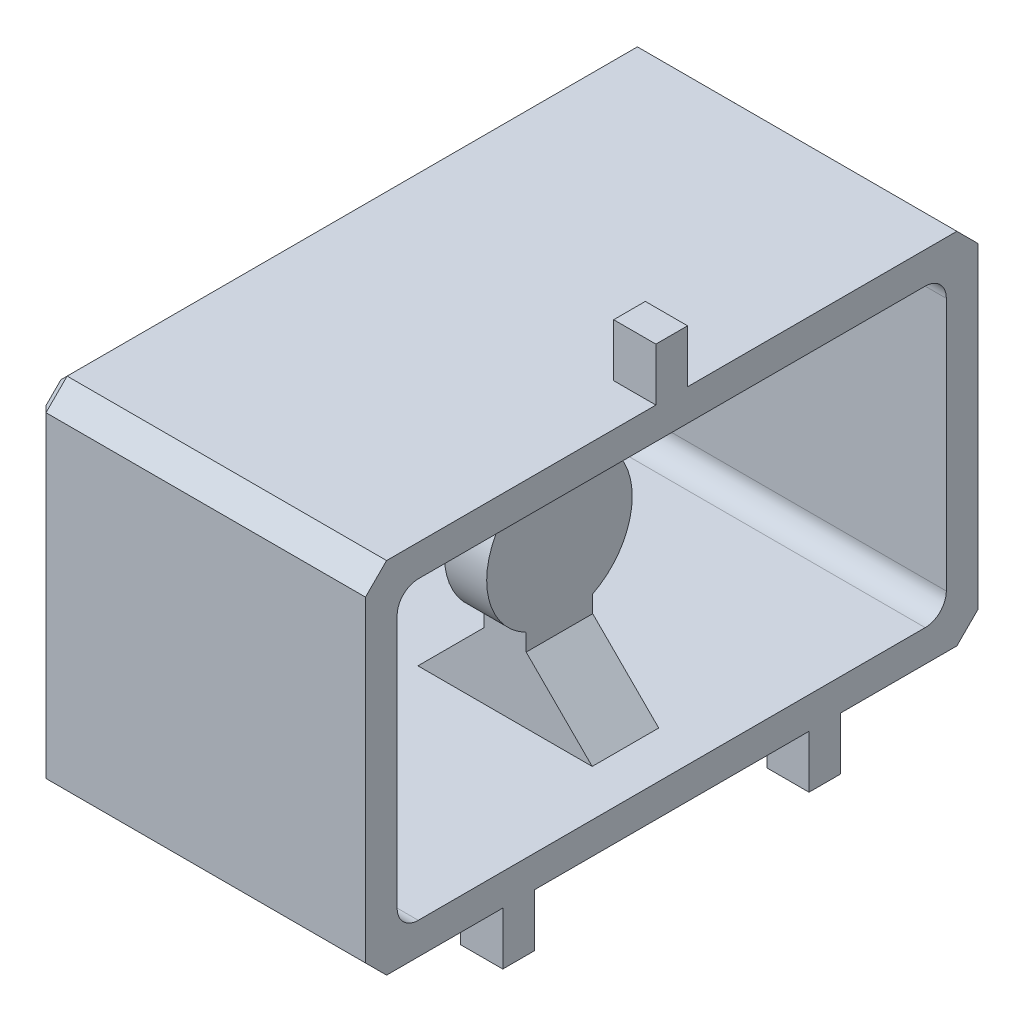
SolidWorks part; units mm, degrees
ref_plane "Front Plane" through (0, 0, 0) normal (0, 0, 1) x (1, 0, 0)
ref_plane "Top Plane" through (0, 0, 0) normal (0, 1, 0) x (1, 0, 0)
ref_plane "Right Plane" through (0, 0, 0) normal (1, 0, 0) x (0, 0, -1)
sketch "Sketch2" plane through (-2.794, 0, 0) normal (1, 0, 0) x (0, 0, -1)
  line L2 (-14.732, -58.674) -> (0, -58.674)
  line L3 (-14.732, -58.674) -> (-14.732, -67.31)
  line L4 (-14.732, -67.31) -> (0, -67.31)
  line L5 (0, -58.674) -> (0, -67.31)
  line L6 (-14.732, -58.674) -> (0, -67.31) construction
  line L7 (-14.732, -67.31) -> (0, -58.674) construction
  point P4 (-7.366, -62.992)
extrude "Extrude-Thin1" add sketch "Sketch2" along normal blind 7.9375 thin thin type one direction reverse wall 0.762
sketch "Sketch3" plane through (5.1435, 0, 0) normal (1, 0, 0) x (0, 0, -1)
  line L4 (-14.732, -58.674) -> (-14.732, -67.31)
  line L5 (-14.732, -67.31) -> (0, -67.31)
  line L6 (0, -67.31) -> (0, -58.674)
  line L7 (0, -58.674) -> (-14.732, -58.674)
  line L8 (-14.732, -58.674) -> (-14.732, -67.31)
  line L9 (-14.732, -67.31) -> (0, -67.31)
  line L10 (0, -67.31) -> (0, -58.674)
  line L11 (0, -58.674) -> (-14.732, -58.674)
  dimension "D1" = 0
extrude "Boss-Extrude1" add sketch "Sketch3" against normal blind 1.27
sketch "Sketch4" plane through (5.1435, 0, 0) normal (1, 0, 0) x (0, 0, -1)
  line L0 (-0.762, -66.548) -> (-4.711, -66.548)
  line L1 (-9.3446, -62.992) -> (-10.021, -62.992) construction
  line L2 (-10.021, -62.992) -> (-10.021, -61.2969) construction
  line L3 (-13.97, -59.436) -> (-10.021, -59.436)
  line L4 (-13.97, -59.436) -> (-13.97, -66.548)
  line L5 (-7.366, -58.674) -> (-7.366, -67.31) construction
  line L6 (0, -58.674) -> (-14.732, -58.674) construction
  line L7 (-14.732, -67.31) -> (0, -67.31) construction
  line L8 (-13.97, -66.548) -> (-10.021, -66.548)
  line L9 (-10.021, -59.436) -> (-10.021, -66.548)
  line L10 (-13.97, -59.436) -> (-10.021, -66.548) construction
  line L11 (-13.97, -66.548) -> (-10.021, -59.436) construction
  line L12 (-0.762, -59.436) -> (-0.762, -66.548)
  line L13 (-0.762, -59.436) -> (-4.711, -59.436)
  line L14 (-4.711, -59.436) -> (-4.711, -66.548)
  arc A0 (-10.021, -64.6783) -> (-10.021, -61.3057) centre (-11.7846, -62.992) ccw construction
  point P20 (-11.9955, -62.992)
extrude "Cut-Extrude1" cut sketch "Sketch4" against normal up to next
sketch "Sketch7" plane through (3.8735, 0, 0) normal (-1, 0, 0) x (0, 0, 1)
  line L0 (7.366, -59.436) -> (7.366, -62.992) construction
  line L1 (4.711, -59.436) -> (10.021, -59.436) construction
  line L2 (7.366, -62.992) -> (4.711, -62.992) construction
  line L3 (4.711, -66.548) -> (4.711, -59.436) construction
  circle A0 centre (7.366, -62.992) radius 1.016
  dimension "D1" = 2.032
extrude "Boss-Extrude2" add sketch "Sketch7" along normal blind 1.27
hole_wizard "#0-80 Tapped Hole1" positions "Sketch6" profile "Sketch5" tap size "#0-80" standard "ANSI Inch" end condition through all
sketch "Sketch6" plane through (5.1435, 0, 0) normal (1, 0, 0) x (0, 0, -1)
  point P0 (-7.366, -62.992)
sketch "Sketch5" plane through (5.1435, -62.992, 7.366) normal (0, 1, 0) x (0, 0, -1)
  line L0 (0, 0) -> (0, 7.9375)
  line L1 (0, 7.9375) -> (0.5956, 7.9375)
  line L2 (0.5956, 7.9375) -> (0.5956, 0)
  line L5 (0.5956, 0) -> (0, 0)
  line L11 (0, -6.35) -> (0, 107.95) construction
  dimension "Thru Tap Drill Dia." = 1.1913
  dimension "Thru Tap Drill Depth" = 7.9375
cosmetic thread "Hole Thread1" parameters "D2"=1.524
sketch "Sketch9" plane through (5.1435, 0, 0) normal (1, 0, 0) x (0, 0, -1)
  line L0 (-7.366, -58.674) -> (-7.366, -57.404)
  line L2 (-14.732, -67.31) -> (-7.366, -67.31) construction
  line L3 (-14.732, -67.31) -> (0, -67.31) construction
  line L4 (-7.366, -67.31) -> (0, -67.31) construction
  line L5 (-11.049, -67.31) -> (-11.049, -68.58)
  line L6 (-3.683, -67.31) -> (-3.683, -68.58)
  line L7 (0, -58.674) -> (-14.732, -58.674) construction
  dimension "D1" = 1.27
  dimension "D2" = 1.27
extrude "Extrude-Thin2" add sketch "Sketch9" against normal blind 1.27 thin thin type mid plane wall 0.762
fillet "Fillet1" radius 0.508 11 edges at (1.1748, -59.436, 13.97) (1.1748, -59.436, 0.762) (1.1748, -66.548, 0.762) (1.1748, -66.548, 13.97) (4.5085, -59.436, 4.711) (4.5085, -66.548, 4.711) (3.8735, -61.976, 7.366)
chamfer "Chamfer1" distance 0.508 angle 45 4 edges at (1.1748, -67.31, 14.732) (1.1748, -67.31, 0) (1.1748, -58.674, 0) (1.1748, -58.674, 14.732)
chamfer "Chamfer2" distance 0.254 angle 45 17 edges at (-2.794, -67.056, 14.478) (-2.794, -67.31, 7.366) (-2.794, -67.056, 0.254) (-2.794, -62.992, 0) (-2.794, -58.928, 0.254) (-2.794, -62.992, 14.732) (-2.794, -58.928, 14.478) (-2.794, -58.674, 7.366) (3.8735, -58.039, 6.985) (3.8735, -57.404, 7.366) (3.8735, -58.039, 7.747) (3.8735, -67.945, 10.668) (3.8735, -68.58, 11.049) (3.8735, -67.945, 11.43) (3.8735, -67.945, 3.302) (3.8735, -68.58, 3.683) (3.8735, -67.945, 4.064)
sketch "Sketch10" plane through (5.1435, 0, 0) normal (1, 0, 0) x (0, 0, -1)
  line L0 (-4.711, -59.944) -> (-4.711, -66.04) construction
  line L1 (-10.021, -66.04) -> (-10.021, -59.944) construction
  line L2 (-4.711, -59.944) -> (-4.711, -66.04)
  line L3 (-10.021, -66.04) -> (-10.021, -59.944)
  line L4 (-10.529, -59.436) -> (-4.203, -59.436)
  line L5 (-4.203, -66.548) -> (-10.529, -66.548)
  arc A0 (-10.529, -66.548) -> (-10.021, -66.04) centre (-10.529, -66.04) ccw construction
  arc A1 (-4.711, -66.04) -> (-4.203, -66.548) centre (-4.203, -66.04) ccw construction
  arc A2 (-4.203, -59.436) -> (-4.711, -59.944) centre (-4.203, -59.944) ccw construction
  arc A3 (-10.021, -59.944) -> (-10.529, -59.436) centre (-10.529, -59.944) ccw construction
  arc A4 (-10.529, -66.548) -> (-10.021, -66.04) centre (-10.529, -66.04) ccw
  arc A5 (-4.711, -66.04) -> (-4.203, -66.548) centre (-4.203, -66.04) ccw
  arc A6 (-4.203, -59.436) -> (-4.711, -59.944) centre (-4.203, -59.944) ccw
  arc A7 (-10.021, -59.944) -> (-10.529, -59.436) centre (-10.529, -59.944) ccw
extrude "Boss-Extrude3" add sketch "Sketch10" against normal blind 1.016 from offset 2.7005 offset against normal yes
extrude "Cut-Extrude2" cut sketch "Sketch10<2>" against normal up to next
sketch "Sketch10<2>" plane through (5.1435, 0, 0) normal (1, 0, 0) x (0, 0, -1) same geometry as "Sketch10"
fillet "Fillet4" [suppressed] radius 2.54
sketch "Sketch11" plane through (2.443, 0, 0) normal (1, 0, 0) x (0, 0, -1)
  line L0 (-13.97, -62.992) -> (-0.762, -62.992) construction
  line L13 (-7.366, -62.992) -> (-7.366, -59.436) construction
  line L14 (-1.27, -59.436) -> (-13.462, -59.436) construction
  line L15 (-8.166, -59.436) -> (-8.166, -61.4356)
  line L16 (-13.97, -59.944) -> (-13.97, -66.04) construction
  line L17 (-0.762, -66.04) -> (-0.762, -59.944) construction
  line L18 (-8.166, -64.5484) -> (-8.166, -66.548)
  line L19 (-10.529, -66.548) -> (-4.203, -66.548)
  line L20 (-4.711, -66.04) -> (-4.711, -59.944)
  line L21 (-4.203, -59.436) -> (-10.529, -59.436)
  line L22 (-10.021, -59.944) -> (-10.021, -66.04)
  line L23 (-10.529, -66.548) -> (-8.166, -66.548)
  line L24 (-4.711, -66.04) -> (-4.711, -59.944)
  line L25 (-4.203, -59.436) -> (-6.566, -59.436)
  line L26 (-10.021, -59.944) -> (-10.021, -66.04)
  line L27 (-8.166, -59.436) -> (-10.529, -59.436)
  line L28 (-6.566, -64.5484) -> (-6.566, -66.548)
  line L29 (-6.566, -59.436) -> (-6.566, -61.4356)
  line L30 (-6.566, -66.548) -> (-4.203, -66.548)
  arc A0 (-8.166, -61.4356) -> (-8.166, -64.5484) centre (-7.366, -62.992) ccw
  arc A1 (-6.566, -61.4356) -> (-6.566, -64.5484) centre (-7.366, -62.992) cw
  arc A12 (-10.529, -66.548) -> (-10.021, -66.04) centre (-10.529, -66.04) ccw
  arc A13 (-4.711, -66.04) -> (-4.203, -66.548) centre (-4.203, -66.04) ccw
  arc A14 (-4.203, -59.436) -> (-4.711, -59.944) centre (-4.203, -59.944) ccw
  arc A15 (-10.021, -59.944) -> (-10.529, -59.436) centre (-10.529, -59.944) ccw
  arc A16 (-10.529, -66.548) -> (-10.021, -66.04) centre (-10.529, -66.04) ccw
  arc A17 (-4.711, -66.04) -> (-4.203, -66.548) centre (-4.203, -66.04) ccw
  arc A18 (-4.203, -59.436) -> (-4.711, -59.944) centre (-4.203, -59.944) ccw
  arc A19 (-10.021, -59.944) -> (-10.529, -59.436) centre (-10.529, -59.944) ccw
  point P23 (-7.366, -62.992)
  dimension "D2" = 3.5
  dimension "D1" = 0
  dimension "D3" = 0.8
extrude "Cut-Extrude3" cut sketch "Sketch11" against normal up to next
chamfer "Chamfer3" distance 1.5875 angle 45 4 edges at (2.443, -59.436, 7.366) (2.443, -66.548, 7.366) (1.427, -66.548, 7.366) (1.427, -59.436, 7.366)
equation "\"D2@Sketch9\"=\"D1@Sketch9\""
